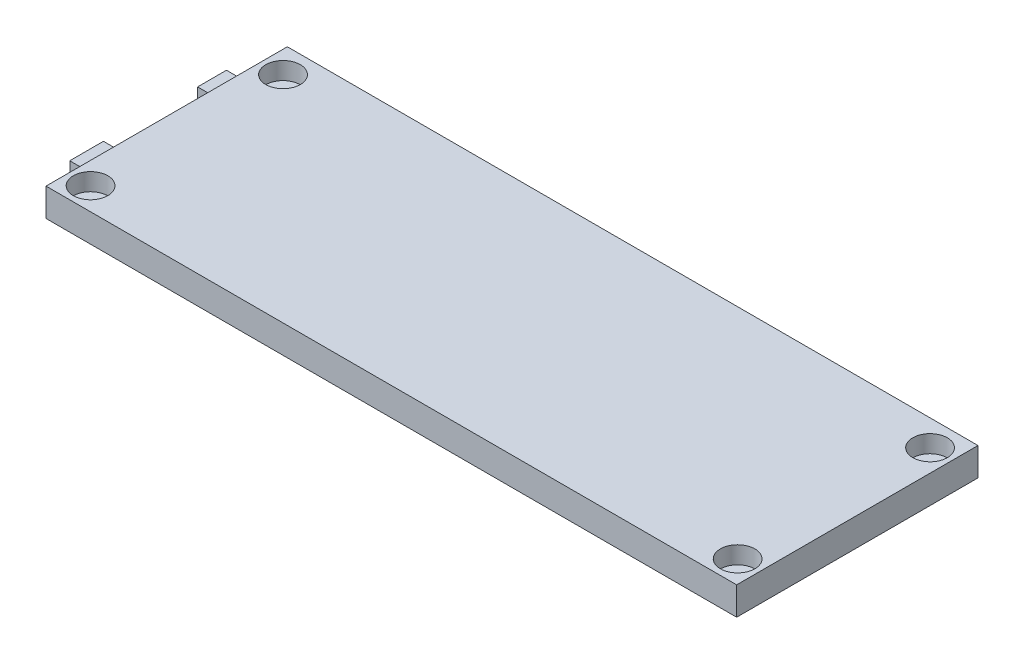
SolidWorks part; units mm, degrees
ref_plane "Front Plane" through (0, 0, 0) normal (0, 0, 1) x (1, 0, 0)
ref_plane "Top Plane" through (0, 0, 0) normal (0, 1, 0) x (1, 0, 0)
ref_plane "Right Plane" through (0, 0, 0) normal (1, 0, 0) x (0, 0, -1)
sketch "Sketch1" plane through (0, 0, 0) normal (0, 1, 0) x (1, 0, 0)
  line L1 (61.4917, -21.4874) -> (-61.4917, -21.4874)
  line L2 (61.4917, -21.4874) -> (61.4917, 21.4874)
  line L3 (61.4917, 21.4874) -> (-61.4917, 21.4874)
  line L4 (-61.4917, -21.4874) -> (-61.4917, 21.4874)
  line L5 (61.4917, -21.4874) -> (-61.4917, 21.4874) construction
  line L6 (61.4917, 21.4874) -> (-61.4917, -21.4874) construction
  point P0 (0, 0)
extrude "Boss-Extrude1" add sketch "Sketch1" along normal blind 5
sketch "Sketch2" plane through (0, 5, 0) normal (0, 1, 0) x (1, 0, 0)
  line L0 (-61.4917, 21.4874) -> (-53.5, 21.4874) construction
  line L1 (61.4917, 21.4874) -> (-61.4917, 21.4874) construction
sketch "Sketch3" plane through (0, 5, 0) normal (0, 1, 0) x (1, 0, 0)
  line L0 (-57.5802, 22.2791) -> (-57.5802, -22.461) construction
  line L1 (57.5677, 22.3499) -> (57.5677, -22.3902) construction
  line L2 (-57.4959, 21.4874) -> (-57.4959, -21.4874) construction
  line L3 (-61.4917, 21.4874) -> (-53.5, 21.4874) construction
  line L4 (-61.4917, -21.4874) -> (61.4917, -21.4874) construction
  circle A0 centre (-57.5802, 16.8075) radius 3.075
  circle A1 centre (-57.5802, -17.461) radius 3.075
  circle A2 centre (57.5677, 16.8783) radius 3.075
  circle A3 centre (57.5677, -17.3902) radius 3.075
extrude "Cut-Extrude1" cut sketch "Sketch3" against normal blind 3.1
sketch "Sketch5" plane through (-61.4917, 0, 0) normal (-1, 0, 0) x (0, 0, 1)
  line L0 (-22.3979, 2.4922) -> (22.3422, 2.4922) construction
  line L1 (-13.7478, 1.7003) -> (-13.7478, 3.7003)
  line L2 (-13.7478, 1.7003) -> (-8.6053, 1.7003)
  line L3 (-8.6053, 1.7003) -> (-8.6053, 3.7003)
  line L4 (-13.7478, 3.7003) -> (-8.6053, 3.7003)
  line L5 (-8.6053, 1.7003) -> (8.1572, 1.7003) construction
  line L9 (14.1572, 3.6937) -> (8.1572, 3.6937)
  line L10 (8.1572, 1.6901) -> (8.1572, 3.6937)
  line L11 (14.1572, 1.6901) -> (8.1572, 1.6901)
  line L12 (14.1572, 1.6901) -> (14.1572, 3.6937)
  line L13 (-21.4874, 2.5) -> (21.4874, 2.5) construction
  line L14 (-21.4874, 5) -> (-21.4874, 0) construction
  line L15 (21.4874, 5) -> (21.4874, 0) construction
  point P2 (-11.2129, 2.4922)
  point P11 (11.1572, 2.4922)
  dimension "D1" = 2
extrude "Boss-Extrude2" add sketch "Sketch5" along normal blind 3.1
